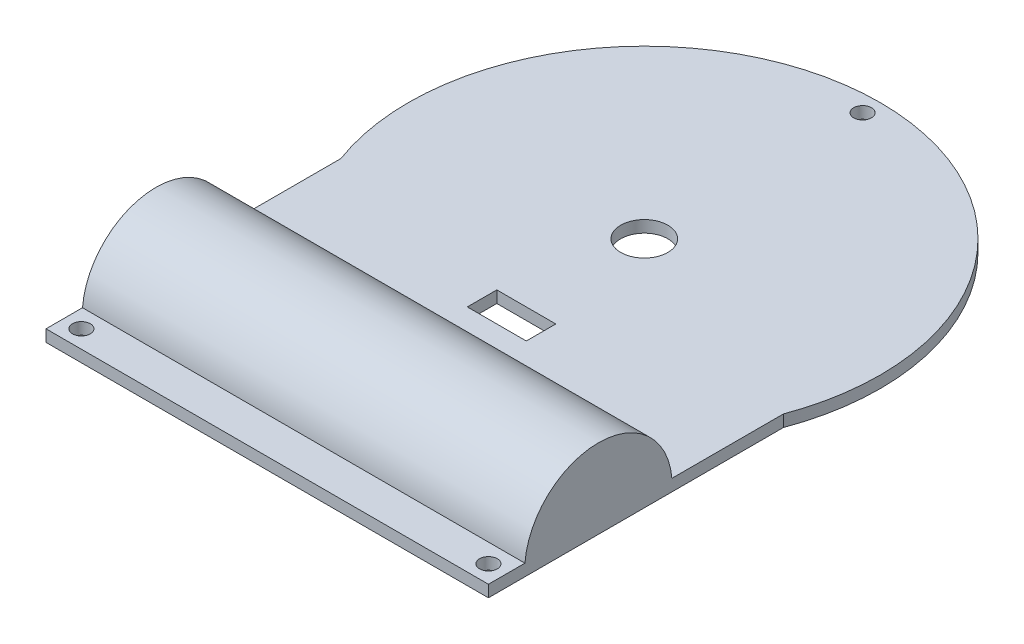
SolidWorks part; units mm, degrees
ref_plane "Front Plane" through (0, 0, 0) normal (0, 0, 1) x (1, 0, 0)
ref_plane "Top Plane" through (0, 0, 0) normal (0, 1, 0) x (1, 0, 0)
ref_plane "Right Plane" through (0, 0, 0) normal (1, 0, 0) x (0, 0, -1)
sketch "Sketch1" plane through (0, 0, 0) normal (0, 1, 0) x (1, 0, 0)
  line L1 (-37.5, -63.9194) -> (37.5, -63.9194)
  line L2 (-37.5, -63.9194) -> (-37.5, -13.9194)
  line L4 (37.5, -63.9194) -> (37.5, -13.9194)
  arc A0 (37.5, -13.9194) -> (-37.5, -13.9194) centre (0, 0) ccw
  dimension "D1" = 80
extrude "Boss-Extrude1" add sketch "Sketch1" along normal blind 2
sketch "Sketch2" plane through (0, 2, 0) normal (0, 1, 0) x (1, 0, 0)
  circle A0 centre (0, 0) radius 4
  dimension "D1" = 8
extrude "Cut-Extrude1" cut sketch "Sketch2" against normal blind 2
sketch "Sketch3" plane through (0, 2, 0) normal (0, 1, 0) x (1, 0, 0)
  line L1 (-5, -20) -> (5, -20)
  line L2 (-5, -20) -> (-5, -25)
  line L3 (-5, -25) -> (5, -25)
  line L4 (5, -20) -> (5, -25)
  circle A0 centre (0, 0) radius 4 construction
  point P4 (0, -20)
  dimension "D3" = 20
  dimension "D1" = 5
  dimension "D2" = 10
extrude "Cut-Extrude2" cut sketch "Sketch3" against normal blind 10
sketch "Sketch7" plane through (0, 2, 0) normal (0, 1, 0) x (1, 0, 0)
  line L1 (-37.5, -63.9194) -> (-31.5, -63.9194)
  line L2 (-37.5, -63.9194) -> (-37.5, -57.9194)
  line L3 (-37.5, -57.9194) -> (-31.5, -57.9194)
  line L4 (-31.5, -63.9194) -> (-31.5, -57.9194)
  line L5 (37.5, -63.9194) -> (31.5, -63.9194)
  line L6 (37.5, -63.9194) -> (37.5, -57.9194)
  line L7 (37.5, -57.9194) -> (31.5, -57.9194)
  line L8 (31.5, -63.9194) -> (31.5, -57.9194)
  line L9 (-3, 40) -> (3, 40)
  line L10 (-3, 40) -> (-3, 34)
  line L11 (-3, 34) -> (3, 34)
  line L12 (3, 40) -> (3, 34)
  circle A0 centre (-34.5, -60.9194) radius 1.5
  circle A1 centre (34.5, -60.9194) radius 1.5
  circle A2 centre (0, 37) radius 1.5
  point P21 (-34.5, -57.9194)
  point P22 (-31.5, -60.9194)
  point P24 (34.5, -57.9194)
  point P25 (31.5, -60.9194)
  point P26 (0, 34)
  point P30 (-3, 37)
  dimension "D1" = 3
  dimension "D2" = 3
  dimension "D3" = 3
  dimension "D4" = 6
  dimension "D5" = 6
  dimension "D6" = 6
  dimension "D7" = 6
  dimension "D8" = 6
  dimension "D9" = 6
extrude "Cut-Extrude3" cut sketch "Sketch7" against normal blind 10 contours A2 | A0 | A1 region at (-34.5, 2, 60.9194) region at (34.5, 2, 60.9194) region at (0, 2, -37)
sketch "Sketch8" plane through (-37.5, 0, 0) normal (-1, 0, 0) x (0, 0, 1)
  circle A0 centre (45.2788, 0.9499) radius 10.5
  dimension "D1" = 21
extrude "Cut-Extrude4" cut sketch "Sketch8" against normal through all
sketch "Sketch9" plane through (-37.5, 0, 0) normal (-1, 0, 0) x (0, 0, 1)
  line L0 (32.815, 0) -> (34.8219, 0)
  line L1 (13.9194, 0) -> (34.8219, 0) construction
  line L2 (55.7358, 0) -> (57.7427, 0)
  arc A0 (55.7358, 0) -> (34.8219, 0) centre (45.2788, 0.9499) ccw
  arc A1 (57.7427, 0) -> (32.815, 0) centre (45.2788, 0.9499) ccw
  dimension "D2" = 2
extrude "Boss-Extrude2" add sketch "Sketch9" against normal up to surface (75 mm away) up to face at (37.5, 1.0001, 24.3611)
sketch "Sketch10" plane through (-37.5, 0, 0) normal (-1, 0, 0) x (0, 0, 1)
  line L0 (32.815, 0) -> (57.7427, 0)
  line L1 (13.9194, 0) -> (34.8219, 0) construction
  line L2 (55.7358, 0) -> (63.9194, 0) construction
  arc A0 (57.7427, 0) -> (32.815, 0) centre (45.2788, 0.9499) ccw
extrude "Boss-Extrude3" add sketch "Sketch10" against normal blind 2
sketch "Sketch11" plane through (37.5, 0, 0) normal (1, 0, 0) x (0, 0, -1)
  line L0 (-57.7427, 0) -> (-32.815, 0)
  line L1 (-63.9194, 0) -> (-55.7358, 0) construction
  arc A0 (-32.815, 0) -> (-57.7427, 0) centre (-45.2788, 0.9499) ccw
extrude "Boss-Extrude4" add sketch "Sketch11" against normal blind 2 contours A0 L0
